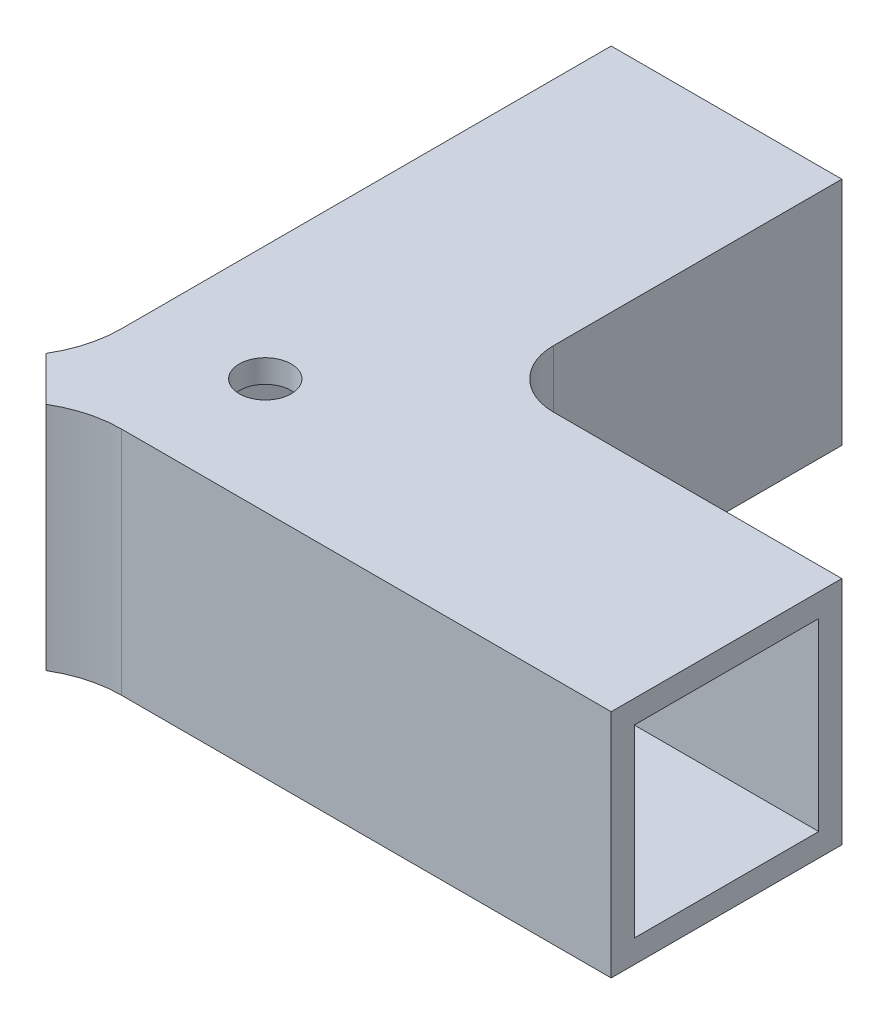
SolidWorks part; units mm, degrees
ref_plane "Front Plane" through (0, 0, 0) normal (0, 0, 1) x (1, 0, 0)
ref_plane "Top Plane" through (0, 0, 0) normal (0, 1, 0) x (1, 0, 0)
ref_plane "Right Plane" through (0, 0, 0) normal (1, 0, 0) x (0, 0, -1)
sketch "Sketch1" plane through (0, 0, 0) normal (0, 0, 1) x (1, 0, 0)
  line L0 (2, 18) -> (18, 18)
  line L1 (0, 0) -> (20, 0)
  line L2 (0, 0) -> (0, 20)
  line L3 (0, 20) -> (20, 20)
  line L4 (20, 0) -> (20, 20)
  line L5 (18, 2) -> (18, 18)
  line L6 (2, 2) -> (18, 2)
  line L7 (2, 2) -> (2, 18)
  dimension "D1" = 20
  dimension "D2" = 20
  dimension "D3" = 2
extrude "Boss-Extrude1" add sketch "Sketch1" along normal blind 30
sketch "Sketch2" plane through (20, 0, 0) normal (1, 0, 0) x (0, 0, -1)
  line L0 (-32, 18) -> (-32, 2)
  line L1 (-30, 20) -> (-50, 20)
  line L2 (-30, 20) -> (-30, 0)
  line L3 (-30, 0) -> (-50, 0)
  line L4 (-50, 20) -> (-50, 0)
  line L5 (-32, 2) -> (-48, 2)
  line L6 (-48, 18) -> (-48, 2)
  line L7 (-32, 18) -> (-48, 18)
  dimension "D1" = 20
  dimension "D2" = 2
extrude "Boss-Extrude2" add sketch "Sketch2" against normal up to surface (20 mm away) and the other way blind 30 up to face at (0, 10, 15)
sketch "Sketch3" plane through (0, 0, 30) normal (0, 0, -1) x (-1, 0, 0)
  line L4 (-2, 2) -> (-2, 18)
  line L5 (-2, 18) -> (-18, 18)
  line L6 (-18, 18) -> (-18, 2)
  line L7 (-18, 2) -> (-2, 2)
  line L8 (-2, 2) -> (-2, 18)
  line L9 (-2, 18) -> (-18, 18)
  line L10 (-18, 18) -> (-18, 2)
  line L11 (-18, 2) -> (-2, 2)
  dimension "D1" = 0
extrude "Cut-Extrude1" cut sketch "Sketch3" against normal up to surface (2 mm away) up to face at (25, 10, 32)
sketch "Sketch4" plane through (0, 0, 0) normal (-1, 0, 0) x (0, 0, 1)
  line L1 (32, 18) -> (48, 18)
  line L2 (32, 18) -> (32, 2)
  line L3 (32, 2) -> (48, 2)
  line L4 (48, 18) -> (48, 2)
extrude "Boss-Extrude3" add sketch "Sketch4" against normal up to surface (2 mm away) up to face at (2, 10, 16)
chamfer "Chamfer1" distance 1 angle 45 1 edges at (0, 10, 50)
sketch "Sketch5" plane through (-24.5, 0, 24.5) normal (-0.7071, 0, 0.7071) x (0.7071, 0, 0.7071)
  line L1 (34.6482, 20) -> (32.6482, 20)
  line L2 (34.6482, 20) -> (34.6482, 0)
  line L3 (34.6482, 0) -> (32.6482, 0)
  line L4 (32.6482, 20) -> (32.6482, 0)
  line L5 (36.0624, 20) -> (38.0624, 20)
  line L6 (36.0624, 20) -> (36.0624, 0)
  line L7 (36.0624, 0) -> (38.0624, 0)
  line L8 (38.0624, 20) -> (38.0624, 0)
  dimension "D1" = 2
  dimension "D2" = 2
extrude "Boss-Extrude4" add sketch "Sketch5" against normal up to surface contours L2 L1 L4 L3 up to face at (0, 10, 24.5)
sketch "Sketch7" plane through (-24.5, 0, 24.5) normal (-0.7071, 0, 0.7071) x (0.7071, 0, 0.7071)
  line L4 (38.0624, 20) -> (36.0624, 20)
  line L5 (38.0624, 0) -> (38.0624, 20)
  line L6 (36.0624, 0) -> (38.0624, 0)
  line L7 (36.0624, 20) -> (36.0624, 0)
  line L8 (38.0624, 20) -> (36.0624, 20)
  line L9 (38.0624, 0) -> (38.0624, 20)
  line L10 (36.0624, 0) -> (38.0624, 0)
  line L11 (36.0624, 20) -> (36.0624, 0)
  line L12 (34.6482, 20) -> (32.6482, 20)
  line L13 (32.6482, 20) -> (32.6482, 0)
  line L14 (32.6482, 0) -> (34.6482, 0)
  line L15 (34.6482, 0) -> (34.6482, 20)
  line L16 (34.6482, 20) -> (32.6482, 20)
  line L17 (32.6482, 20) -> (32.6482, 0)
  line L18 (32.6482, 0) -> (34.6482, 0)
  line L19 (34.6482, 0) -> (34.6482, 20)
  dimension "D1" = 0
  dimension "D2" = 0
extrude "Boss-Extrude6" add sketch "Sketch7" against normal up to surface contours L8 L11 L10 L9 up to face at (25.5, 10, 50)
fillet "Fillet1" radius 10 2 edges at (0, 10, 46.1716) (3.8284, 10, 50)
fillet "Fillet2" radius 3 1 edges at (18, 10, 32)
sketch "Sketch8" plane through (0, 20, 0) normal (0, 1, 0) x (1, 0, 0)
  circle A0 centre (10, -40) radius 2.25 construction
  circle A1 centre (10, -40) radius 2.25
extrude "Cut-Extrude2" cut sketch "Sketch8" against normal up to surface (20 mm away) up to face at (16.5325, 0, 33.4675)
fillet "Fillet3" radius 5 1 edges at (20, 10, 30)
